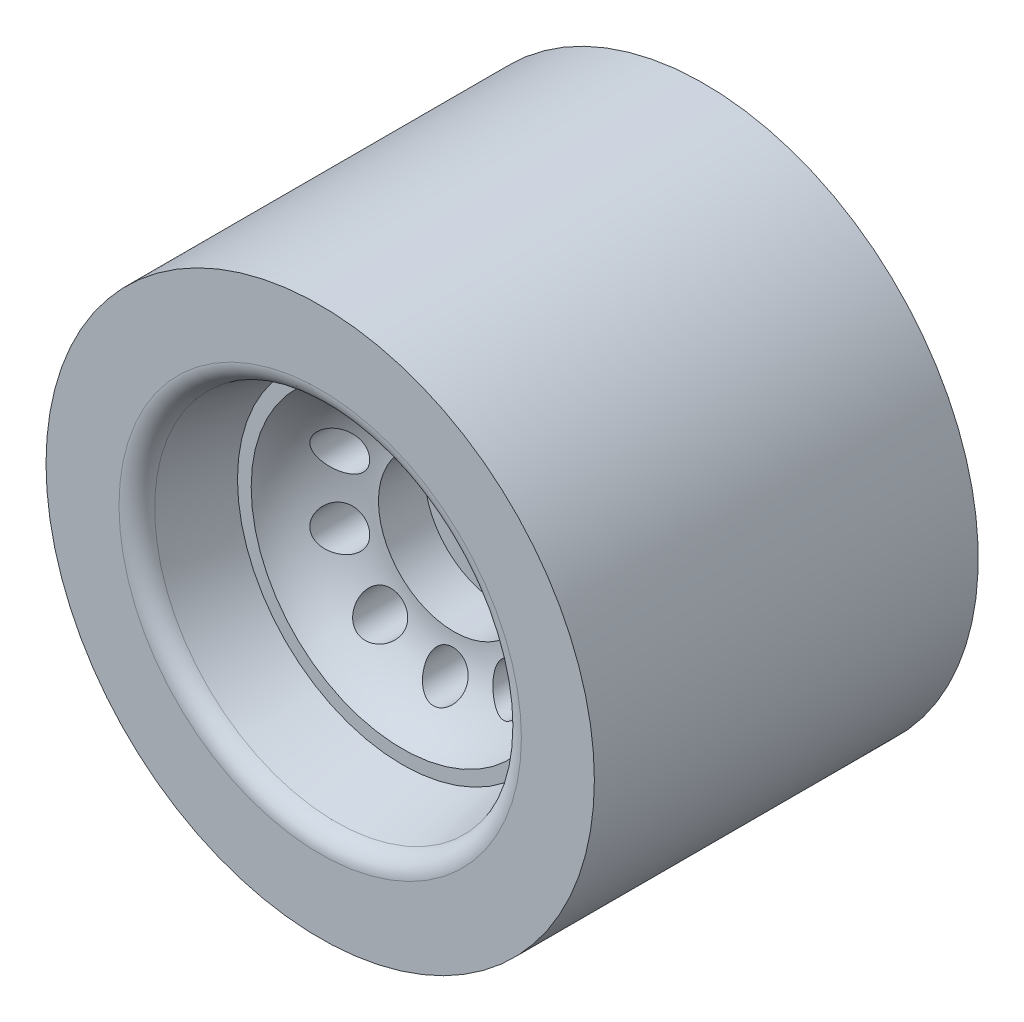
SolidWorks part; units mm, degrees
material "폴리우레탄(11671)"
ref_plane "정면" through (0, 0, 0) normal (0, 0, 1) x (1, 0, 0)
ref_plane "윗면" through (0, 0, 0) normal (0, 1, 0) x (1, 0, 0)
ref_plane "우측면" through (0, 0, 0) normal (1, 0, 0) x (0, 0, -1)
sketch "스케치1" plane through (0, 0, 0) normal (0, 0, 1) x (1, 0, 0)
  circle A0 centre (0, 0) radius 40
  dimension "D1" = 80
extrude "보스-돌출1" add sketch "스케치1" along normal mid plane 56
sketch "스케치2" plane through (0, 0, 28) normal (0, 0, 1) x (1, 0, 0)
  circle A0 centre (0, 0) radius 8.5
  dimension "D1" = 17
extrude "컷-돌출1" cut sketch "스케치2" against normal through all
sketch "스케치4" plane through (0, 0, 0) normal (1, 0, 0) x (0, 0, -1)
  line L0 (28, 0) -> (-28, 0) construction
  line L1 (28, -40) -> (28, 40) construction
  line L2 (-28, 40) -> (-28, -40) construction
  line L3 (0, 0) -> (0, -40) construction
  line L4 (-28, -40) -> (28, -40) construction
  line L5 (28, 40) -> (26.6, 33.9)
  line L7 (15.1, 0) -> (28, 0)
  line L8 (15.1, 0) -> (15.1, 11)
  line L9 (26.6, 33.9) -> (25.6, 33.4)
  line L10 (28, 0) -> (28, 40)
  line L11 (-28, 0) -> (-28, 27)
  line L12 (-28, 27) -> (-16.0084, 24.06)
  line L13 (-8.5, 11) -> (-8.5, 0)
  line L14 (-8.5, 0) -> (-28, 0)
  line L15 (-16.0084, 24.06) -> (-16.0084, 22.06)
  arc A0 (22.6084, 22.06) -> (24.2058, 28.6555) centre (43.7359, 20.4341) cw
  arc A1 (15.1, 11) -> (22.6084, 22.06) centre (27, 11) cw
  arc A2 (24.2058, 28.6555) -> (25.6, 33.4) centre (3.9291, 37.191) ccw
  arc A3 (-16.0084, 22.06) -> (-8.5, 11) centre (-20.4, 11) cw
  point P27 (0, 0)
  point P30 (28.1584, 0)
  dimension "D5" = 11.9
  dimension "D4" = 0.5
  dimension "D9" = 21.19
  dimension "D12" = 22
  dimension "D14" = 13
  dimension "D13" = 11.9
  dimension "D2" = 22.06
  dimension "D3" = 6.1
  dimension "D6" = 11
  dimension "D7" = 11.5
  dimension "D8" = 1
  dimension "D15" = 19.5
  dimension "D16" = 2
  dimension "D17" = 1.4
  dimension "D18" = 11.3445
revolve "컷-회전1" cut sketch "스케치4" angle 360 about L0
sketch "스케치5" plane through (0, 0, 0) normal (0, 0, 1) x (1, 0, 0)
  line L0 (0, 0) -> (0, 40) construction
  circle A0 centre (0, 0) radius 40 construction
  circle A1 centre (0, 15.875) radius 3
  dimension "D1" = 6
  dimension "D2" = 15.875
extrude "컷-돌출2" cut sketch "스케치5" against normal through all both and the other way through all
pattern_circular "원형 패턴1" count 10 over 360 about axis through (0, 0, -28) along (0, 0, 1) of "컷-돌출2"
fillet "필렛1" radius 3 1 edges at (-27, 0, 28)
sketch "스케치6" plane through (0, 0, 8.5) normal (0, 0, 1) x (1, 0, 0)
  circle A0 centre (0, 0) radius 11
  dimension "D1" = 22
extrude "컷-돌출3" cut sketch "스케치6" against normal blind 6.75
sketch "스케치7" plane through (0, 0, -15.1) normal (0, 0, -1) x (-1, 0, 0)
  circle A0 centre (0, 0) radius 11
  dimension "D1" = 22
extrude "컷-돌출4" cut sketch "스케치7" against normal blind 6.75
